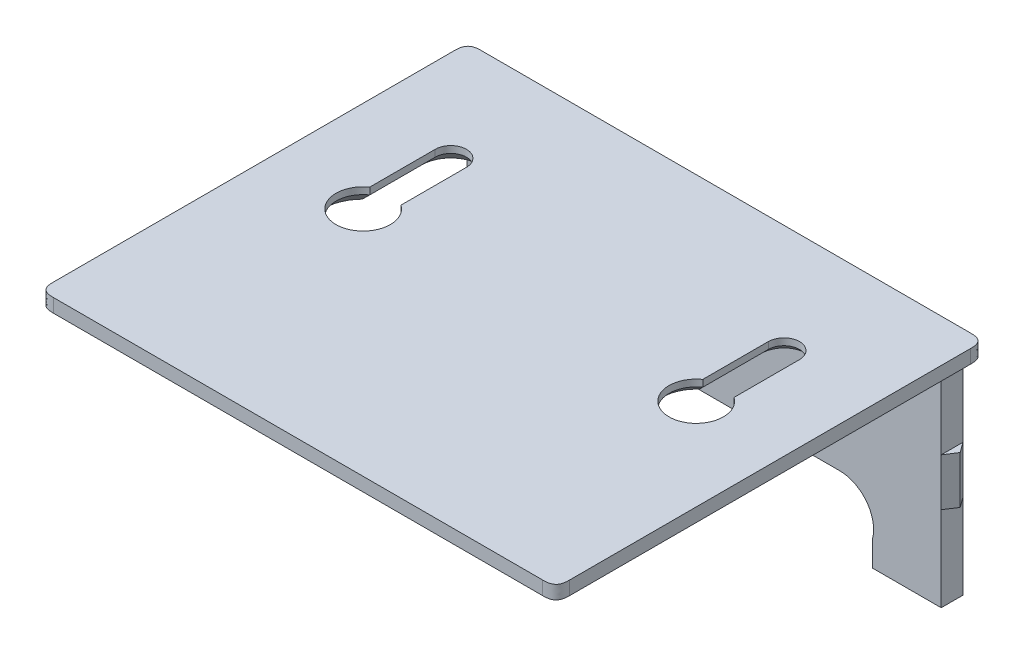
SolidWorks part; units mm, degrees
ref_plane "Front Plane" through (0, 0, 0) normal (0, 0, 1) x (1, 0, 0)
ref_plane "Top Plane" through (0, 0, 0) normal (0, 1, 0) x (1, 0, 0)
ref_plane "Right Plane" through (0, 0, 0) normal (1, 0, 0) x (0, 0, -1)
sketch "Sketch1" plane through (0, 0, 0) normal (0, 1, 0) x (1, 0, 0)
  line L1 (-38, 31.5) -> (38, 31.5)
  line L2 (-38, 31.5) -> (-38, -31.5)
  line L3 (-38, -31.5) -> (38, -31.5)
  line L4 (38, 31.5) -> (38, -31.5)
  line L5 (0, -31.5) -> (0, 31.5) construction
  line L6 (-38, 0) -> (38, 0) construction
  point P0 (0, 0)
  dimension "D1" = 76
  dimension "D2" = 63
extrude "Boss-Extrude1" add sketch "Sketch1" along normal blind 2
sketch "Sketch2" plane through (0, 0, 0) normal (0, 1, 0) x (1, 0, 0)
  line L0 (38, 31.5) -> (-38, 31.5) construction
  line L1 (-34.8, -28.3) -> (34.8, -28.3)
  line L2 (-34.8, -28.3) -> (-34.8, 28.3)
  line L3 (-34.8, 28.3) -> (34.8, 28.3)
  line L4 (34.8, -28.3) -> (34.8, 28.3)
  line L5 (0, 28.3) -> (0, -28.3) construction
  line L6 (-34.8, 0) -> (34.8, 0) construction
  line L7 (-38, 31.5) -> (-38, -31.5) construction
  point P0 (0, 0)
  dimension "D1" = 3.2
  dimension "D2" = 3.2
extrude "Boss-Extrude2" add sketch "Sketch2" against normal blind 1
sketch "Sketch3" plane through (0, 0, 0) normal (0, -1, 0) x (1, 0, 0)
  line L0 (38, -31.5) -> (-38, -31.5) construction
  line L1 (-34.9, -31.5) -> (34.9, -31.5)
  line L2 (-34.9, -31.5) -> (-34.9, -28.3)
  line L3 (-34.9, -28.3) -> (34.9, -28.3)
  line L4 (34.9, -31.5) -> (34.9, -28.3)
  line L5 (0, -28.3) -> (0, -31.5) construction
  line L6 (-34.9, -29.9) -> (34.9, -29.9) construction
  line L7 (34.8, -28.3) -> (-34.8, -28.3) construction
  line L8 (-38, -31.5) -> (-38, 31.5) construction
  line L9 (38, 31.5) -> (38, -31.5) construction
  point P560 (0, -29.9)
  dimension "D1" = 3.1
  dimension "D2" = 3.1
extrude "Boss-Extrude3" add sketch "Sketch3" along normal blind 32
ref_plane "Plane1" through (0, 0, -1.5) normal (0, 0, 1) x (1, 0, 0)
sketch "Sketch4" plane through (0, 0, -1.5) normal (0, 0, 1) x (1, 0, 0)
  line L0 (-34.8, 0) -> (-36, -1.5)
  line L1 (-36, -1.5) -> (-34.8, -3)
  line L2 (-34.8, -3) -> (-33.3, -3)
  line L3 (-33.3, -3) -> (-33.3, 0)
  line L4 (-34.8, 0) -> (34.8, 0) construction
  line L5 (-33.3, 0) -> (-34.8, 0)
  line L6 (0, 0) -> (0, -13.9424) construction
  line L7 (33.3, 0) -> (34.8, 0)
  line L8 (33.3, -3) -> (33.3, 0)
  line L9 (34.8, -3) -> (33.3, -3)
  line L10 (36, -1.5) -> (34.8, -3)
  line L11 (34.8, 0) -> (36, -1.5)
  dimension "D1" = 1.5
  dimension "D2" = 3
  dimension "D3" = 1.2
  dimension "D4" = 1.5
extrude "Boss-Extrude4" add sketch "Sketch4" along normal mid plane 7
sketch "Sketch5" plane through (0, 0, 0) normal (1, 0, 0) x (0, 0, -1)
  line L0 (-28.3, 0) -> (-29.5, -1.5)
  line L1 (-29.5, -1.5) -> (-28.3, -3)
  line L2 (-28.3, -3) -> (-27.3, -3)
  line L3 (-27.3, -3) -> (-27.3, 0)
  line L4 (-31.5, 0) -> (31.5, 0) construction
  line L5 (-27.3, 0) -> (-28.3, 0)
  dimension "D1" = 1
  dimension "D2" = 1.2
  dimension "D3" = 3
  dimension "D4" = 1.5
extrude "Boss-Extrude5" add sketch "Sketch5" along normal mid plane 7
ref_plane "Plane2" through (0, -16, 0) normal (0, -1, 0) x (-1, 0, 0)
sketch "Sketch6" plane through (0, -16, 0) normal (0, -1, 0) x (-1, 0, 0)
  line L0 (-34.9, 31.5) -> (-36, 30)
  line L1 (-36, 30) -> (-34.9, 28.3)
  line L2 (-34.9, 28.3) -> (-34.9, 31.5)
  line L3 (0, 0) -> (0, 15.5484) construction
  line L4 (34.9, 28.3) -> (34.9, 31.5)
  line L5 (36, 30) -> (34.9, 28.3)
  line L6 (34.9, 31.5) -> (36, 30)
  dimension "D1" = 1.1
  dimension "D2" = 1.5
extrude "Boss-Extrude6" add sketch "Sketch6" along normal mid plane 7
sketch "Sketch7" plane through (0, -1, 0) normal (0, -1, 0) x (1, 0, 0)
  line L0 (-26.822, -5.8793) -> (-26.822, -15.5165)
  line L1 (-22.222, -5.8793) -> (-22.222, -15.5165)
  line L2 (0, 0) -> (0, 14.6331) construction
  line L3 (22.222, -5.8793) -> (22.222, -15.5165)
  line L4 (26.822, -5.8793) -> (26.822, -15.5165)
  arc A0 (-26.822, -5.8793) -> (-22.222, -5.8793) centre (-24.522, -2.6067) cw
  arc A1 (-22.222, -15.5165) -> (-26.822, -15.5165) centre (-24.522, -15.5165) cw
  arc A2 (22.222, -15.5165) -> (26.822, -15.5165) centre (24.522, -15.5165) ccw
  arc A3 (26.822, -5.8793) -> (22.222, -5.8793) centre (24.522, -2.6067) ccw
  dimension "D1" = 2.3
  dimension "D2" = 4
extrude "Cut-Extrude1" cut sketch "Sketch7" against normal blind 7
chamfer "Chamfer1" distance 2 angle 45 8 edges at (26.822, -1, -10.6979) (24.522, -1, -17.8165) (22.222, -1, -10.6979) (24.522, -1, 1.3933) (-22.222, -1, -10.6979) (-24.522, -1, -17.8165) (-26.822, -1, -10.6979) (-24.522, -1, 1.3933)
fillet "Fillet1" radius 2 4 edges at (38, 1, 31.5) (38, 1, -31.5) (-38, 1, 31.5) (-38, 1, -31.5) curvature continuous yes
sketch "Sketch8" plane through (0, 0, -31.5) normal (0, 0, -1) x (-1, 0, 0)
  line L0 (-34.9, -20) -> (34.9, -20) construction
  line L1 (-34.9, -32) -> (-34.9, -19.5) construction
  line L2 (34.9, -32) -> (34.9, -19.5) construction
  line L3 (34.9, -32) -> (-34.9, -32) construction
  line L4 (-19.9507, -27) -> (-11.9507, -27) construction
  line L5 (-19.9507, -22) -> (-11.9507, -22)
  line L6 (-19.9507, -32) -> (-11.9507, -32)
  line L7 (34.9, -12.5) -> (34.9, 0) construction
  line L8 (-34.9, -12.5) -> (-34.9, 0) construction
  line L9 (-27.4, 0.5) -> (-15.4, 0.5)
  line L10 (-27.4, 0.5) -> (-27.4, -8.5)
  line L11 (-27.4, -8.5) -> (-15.4, -8.5)
  line L12 (-15.4, 0.5) -> (-15.4, -8.5)
  line L13 (-21.4, -8.5) -> (-21.4, 0.5) construction
  line L14 (-27.4, -4) -> (-15.4, -4) construction
  arc A0 (-19.9507, -22) -> (-19.9507, -32) centre (-19.9507, -27) ccw
  arc A1 (-11.9507, -32) -> (-11.9507, -22) centre (-11.9507, -27) ccw
  circle A2 centre (14.4, -21.8) radius 7
  point P10 (-15.9507, -27)
  point P211 (-21.4, -4)
  dimension "D2" = 5
  dimension "D6" = 14
  dimension "D1" = 12
  dimension "D4" = 8
  dimension "D7" = 20.5
  dimension "D8" = 1.8
  dimension "D9" = 12
  dimension "D10" = 9
  dimension "D11" = 16
  dimension "D12" = 13.5
extrude "Cut-Extrude2" cut sketch "Sketch8" against normal up to surface (3.2 mm away) and the other way through all from offset 0 up to face at (0, -10.8333, -28.3)
sketch "Sketch9" plane through (0, -1, 0) normal (0, -1, 0) x (1, 0, 0)
  line L0 (34.8, -28.3) -> (27.4, -28.3) construction
  line L1 (15.4, -28.3) -> (33.261, -28.3)
  line L2 (15.4, -28.3) -> (15.4, -0.3)
  line L3 (15.4, -0.3) -> (33.261, -0.3)
  line L4 (33.261, -28.3) -> (33.261, -0.3)
  line L5 (24.3305, -0.3) -> (24.3305, -28.3) construction
  line L6 (15.4, -14.3) -> (33.261, -14.3) construction
  point P412 (24.3305, -14.3)
  dimension "D1" = 28
extrude "Cut-Extrude3" cut sketch "Sketch9" against normal blind 1
sketch "Sketch10" plane through (0, -1, 0) normal (0, -1, 0) x (1, 0, 0)
  line L0 (34.8, 28.3) -> (34.8, 2) construction
  line L1 (-34.8, 27.3) -> (34.8, 27.3)
  line L2 (-34.8, 27.3) -> (-34.8, 19.3)
  line L3 (-34.8, 19.3) -> (34.8, 19.3)
  line L4 (34.8, 27.3) -> (34.8, 19.3)
  line L5 (0, 19.3) -> (0, 27.3) construction
  line L6 (-34.8, 23.3) -> (34.8, 23.3) construction
  line L8 (3.5, 27.3) -> (-3.5, 27.3) construction
  line L9 (-34.8, 2) -> (-34.8, 28.3) construction
  line L10 (34.8, 28.3) -> (34.8, 2) construction
  point P128 (0, 23.3)
  dimension "D1" = 8
extrude "Cut-Extrude4" cut sketch "Sketch10" against normal blind 2
chamfer "Chamfer2" distance 1 angle 60 1 edges at (0, -3, 27.3) first distance on face at (0, -3, 27.8)
sketch "Sketch11" plane through (0, 0, -31.5) normal (0, 0, -1) x (-1, 0, 0)
  line L0 (-24.7989, -28.2226) -> (-24.7989, -36.2743)
  line L1 (-24.7989, -36.2743) -> (17.4169, -36.2743)
  line L2 (17.4169, -36.2743) -> (17.4169, -28.1165)
  line L3 (-24.7989, -28.2226) -> (-13.0829, -28.2226)
  line L4 (-13.0829, -28.2226) -> (-13.0829, -22)
  line L5 (-19.9507, -22) -> (-11.9507, -22) construction
  line L6 (-13.0829, -22) -> (7.4029, -22)
  line L7 (7.4029, -22) -> (17.4169, -28.1165)
  circle A1 centre (14.4, -21.8) radius 7 construction
  arc A2 (-19.9507, -22) -> (-19.9507, -32) centre (-19.9507, -27) ccw construction
extrude "Cut-Extrude5" cut sketch "Sketch11" against normal up to surface (3.2 mm away) up to face at (9.8148, -11.6818, -28.3)
